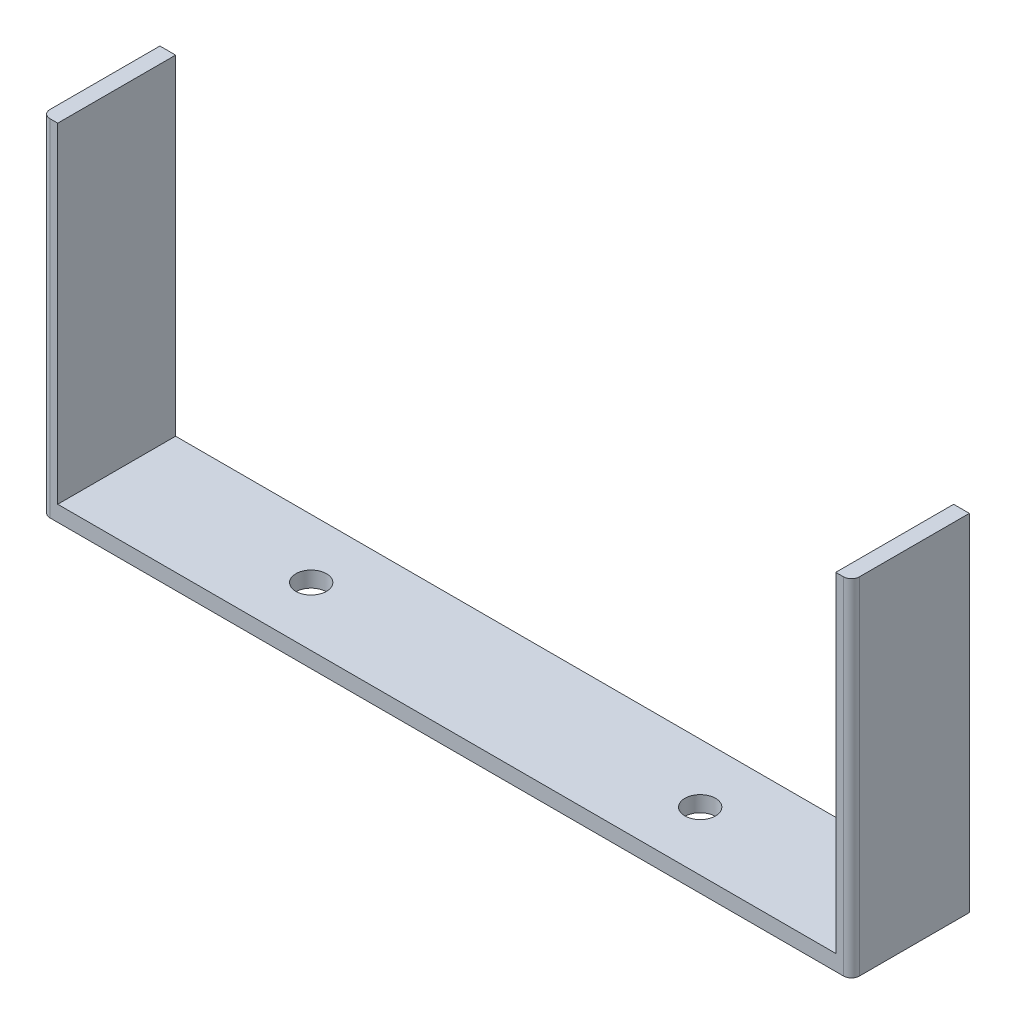
SolidWorks part; units mm, degrees
ref_plane "Plano frontal" through (0, 0, 0) normal (0, 0, 1) x (1, 0, 0)
ref_plane "Plano superior" through (0, 0, 0) normal (0, 1, 0) x (1, 0, 0)
ref_plane "Plano direito" through (0, 0, 0) normal (1, 0, 0) x (0, 0, -1)
sketch "Esboço1" plane through (0, 0, 0) normal (0, 1, 0) x (1, 0, 0)
  line L1 (51.5, -7.5) -> (-51.5, -7.5)
  line L2 (51.5, -7.5) -> (51.5, 7.5)
  line L3 (51.5, 7.5) -> (-51.5, 7.5)
  line L4 (-51.5, -7.5) -> (-51.5, 7.5)
  line L5 (51.5, -7.5) -> (-51.5, 7.5) construction
  line L6 (51.5, 7.5) -> (-51.5, -7.5) construction
  point P0 (0, 0)
  dimension "D1" = 103
  dimension "D2" = 15
extrude "Ressalto-extrusão1" add sketch "Esboço1" against normal blind 2
sketch "Esboço2" plane through (0, 0, 0) normal (0, 1, 0) x (1, 0, 0)
  line L22 (-51.5, 7.5) -> (-51.5, -7.5) construction
  line L23 (-51.5, 7.5) -> (-51.5, -7.5)
  line L24 (-49.5, 7.5) -> (-49.5, -7.5)
  line L25 (-49.5, 7.5) -> (-51.5, 7.5)
  line L26 (-49.5, -7.5) -> (-51.5, -7.5)
  line L27 (0, 0) -> (0, -7.5) construction
  line L28 (-51.5, -7.5) -> (51.5, -7.5) construction
  line L29 (49.5, -7.5) -> (51.5, -7.5)
  line L30 (49.5, 7.5) -> (51.5, 7.5)
  line L31 (49.5, 7.5) -> (49.5, -7.5)
  line L32 (51.5, 7.5) -> (51.5, -7.5)
  dimension "D1" = 2
extrude "Ressalto-extrusão2" add sketch "Esboço2" along normal blind 42
sketch "Esboço4" plane through (0, 0, 0) normal (0, 1, 0) x (1, 0, 0)
  line L0 (0, 0) -> (49.5, 0) construction
  line L1 (49.5, 7.5) -> (49.5, -7.5) construction
  line L2 (0, 0) -> (0, 7.5) construction
  line L3 (49.5, 7.5) -> (-49.5, 7.5) construction
  circle A0 centre (24.75, 0) radius 1.95
  circle A1 centre (-24.75, 0) radius 1.95
  dimension "D1" = 3.9
extrude "Corte-extrusão1" cut sketch "Esboço4" against normal blind 2
fillet "Filete1" radius 1 2 edges at (51.5, 20, 7.5) (-51.5, 20, 7.5)
